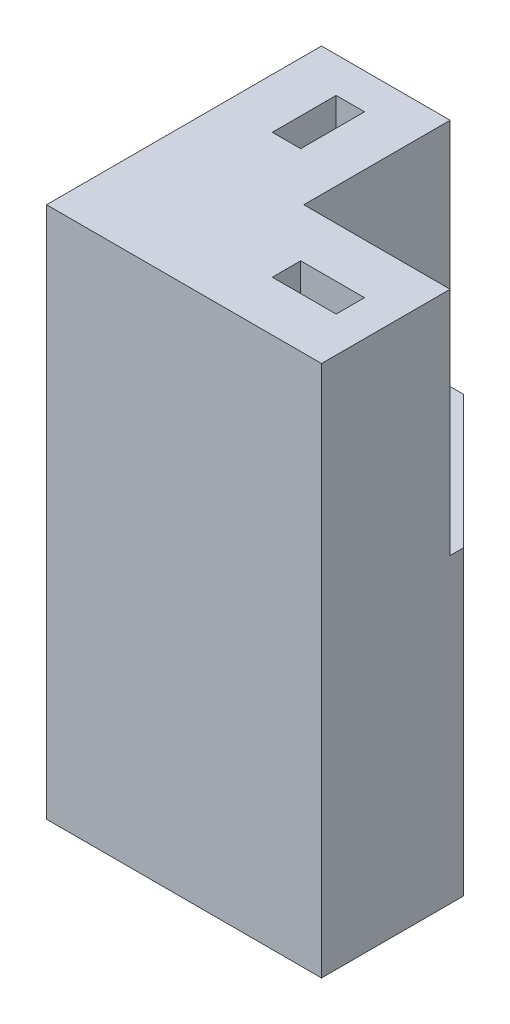
SolidWorks part; units mm, degrees
ref_plane "Front Plane" through (0, 0, 0) normal (0, 0, 1) x (1, 0, 0)
ref_plane "Top Plane" through (0, 0, 0) normal (0, 1, 0) x (1, 0, 0)
ref_plane "Right Plane" through (0, 0, 0) normal (1, 0, 0) x (0, 0, -1)
sketch "Sketch3" plane through (0, 0, 0) normal (0, 1, 0) x (1, 0, 0)
  line L1 (-9.8425, -9.8425) -> (9.8425, -9.8425)
  line L2 (-9.8425, -9.8425) -> (-9.8425, 9.8425)
  line L3 (-9.8425, 9.8425) -> (9.8425, 9.8425)
  line L4 (9.8425, -9.8425) -> (9.8425, 9.8425)
  line L5 (-9.8425, -9.8425) -> (9.8425, 9.8425) construction
  line L6 (-9.8425, 9.8425) -> (9.8425, -9.8425) construction
  point P0 (0, 0)
  dimension "D1" = 19.685
  dimension "D2" = 19.685
extrude "Boss-Extrude2" add sketch "Sketch3" along normal blind 38.1
sketch "Sketch4" plane through (0, 38.1, 0) normal (0, 1, 0) x (1, 0, 0)
  line L0 (9.8425, 9.8425) -> (0, 9.8425)
  line L1 (9.8425, 9.8425) -> (-9.8425, 9.8425) construction
  line L2 (0, 9.8425) -> (0, 0)
  line L3 (0, 0) -> (9.8425, 0)
  line L4 (9.8425, -9.8425) -> (9.8425, 9.8425) construction
  line L5 (9.8425, 0) -> (9.8425, 9.8425)
sketch "Sketch6" plane through (0, 38.1, 0) normal (0, 1, 0) x (1, 0, 0)
  line L0 (9.8425, -0.635) -> (-0.635, -0.635)
  line L1 (9.8425, -9.8425) -> (9.8425, 9.8425) construction
  line L2 (-0.635, -0.635) -> (-0.635, 9.8425)
  line L3 (9.8425, 9.8425) -> (-9.8425, 9.8425) construction
  line L4 (9.8425, 9.8425) -> (0, 9.8425) construction
  line L5 (-0.635, 9.8425) -> (9.8425, 9.8425)
  line L6 (9.8425, 9.8425) -> (9.8425, -0.635)
  dimension "D1" = 10.4775
  dimension "D2" = 10.4775
extrude "Cut-Extrude3" cut sketch "Sketch6" against normal blind 16.51
sketch "Sketch7" plane through (0, 38.1, 0) normal (0, 1, 0) x (1, 0, 0)
  line L0 (-5.2387, 9.8425) -> (-5.2387, -9.8425) construction
  line L1 (-0.635, 9.8425) -> (-9.8425, 9.8425) construction
  line L2 (-9.8425, -9.8425) -> (9.8425, -9.8425) construction
  line L3 (9.8425, -5.2387) -> (-9.8425, -5.2388) construction
  line L4 (9.8425, -9.8425) -> (9.8425, -0.635) construction
  line L5 (-9.8425, 9.8425) -> (-9.8425, -9.8425) construction
  line L7 (-6.2547, 2.7305) -> (-4.2227, 2.7305)
  line L8 (-6.2547, 2.7305) -> (-6.2547, 7.3025)
  line L9 (-6.2547, 7.3025) -> (-4.2227, 7.3025)
  line L10 (-4.2227, 2.7305) -> (-4.2227, 7.3025)
  line L11 (-6.2547, 2.7305) -> (-4.2227, 7.3025) construction
  line L12 (-6.2547, 7.3025) -> (-4.2227, 2.7305) construction
  line L13 (2.7305, -6.2547) -> (7.3025, -6.2547)
  line L14 (2.7305, -6.2547) -> (2.7305, -4.2227)
  line L15 (2.7305, -4.2227) -> (7.3025, -4.2227)
  line L16 (7.3025, -6.2547) -> (7.3025, -4.2227)
  line L17 (2.7305, -6.2547) -> (7.3025, -4.2227) construction
  line L18 (2.7305, -4.2227) -> (7.3025, -6.2547) construction
  point P12 (-5.2387, 5.0165)
  point P17 (5.0165, -5.2388)
  dimension "D1" = 2.032
  dimension "D2" = 4.572
  dimension "D3" = 2.54
  dimension "D6" = 2.54
extrude "Cut-Extrude4" cut sketch "Sketch7" against normal blind 5.08
chamfer "Chamfer1" distance 9.525 angle 45 1 edges at (9.8425, 10.795, -9.8425)
